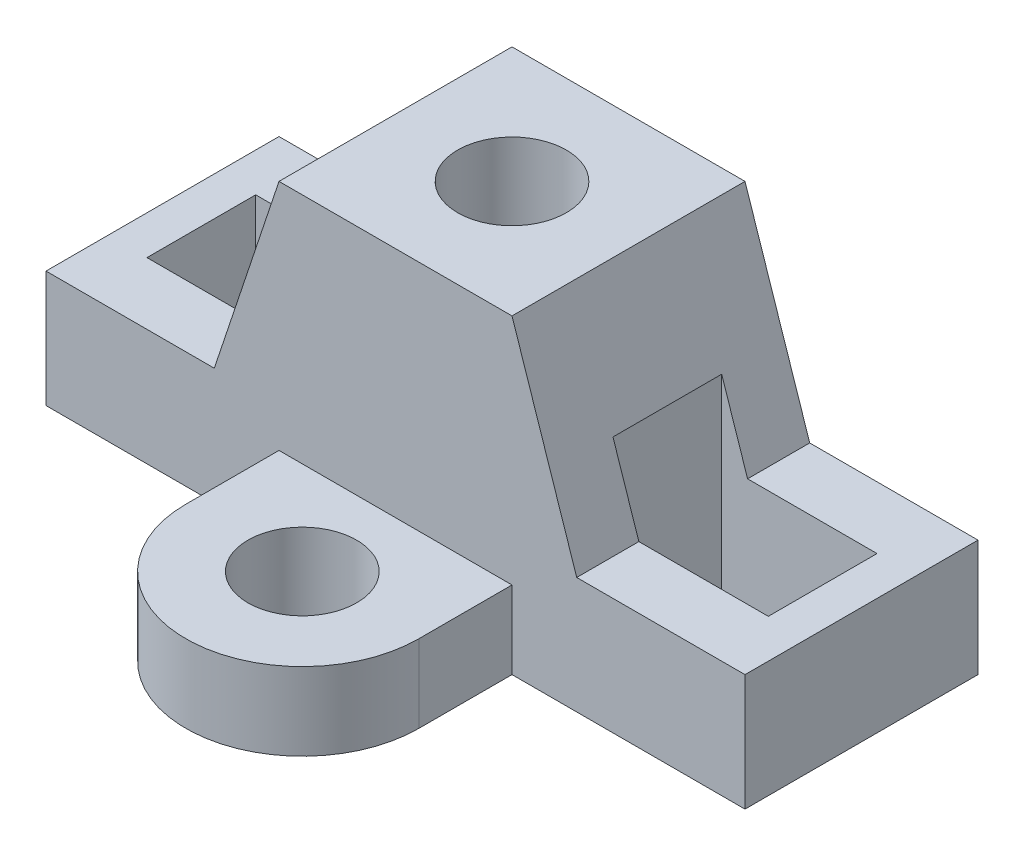
SolidWorks part; units mm, degrees
ref_plane "Front Plane" through (0, 0, 0) normal (0, 0, 1) x (1, 0, 0)
ref_plane "Top Plane" through (0, 0, 0) normal (0, 1, 0) x (1, 0, 0)
ref_plane "Right Plane" through (0, 0, 0) normal (1, 0, 0) x (0, 0, -1)
sketch "Sketch1" plane through (0, 0, 0) normal (0, 1, 0) x (1, 0, 0)
  line L0 (15, 0) -> (15, 12)
  line L1 (-15, 0) -> (-15, 12)
  line L2 (-15, 12) -> (15, 12)
  line L3 (-15, 12) -> (-15, 42)
  line L4 (-15, 42) -> (15, 42)
  line L5 (15, 42) -> (15, 12)
  line L6 (-15, 12) -> (15, 12)
  line L7 (15, 12) -> (45, 12)
  line L8 (-15, 12) -> (-45, 12)
  line L9 (-45, 12) -> (-45, 42)
  line L10 (-45, 42) -> (-15, 42)
  line L11 (15, 42) -> (45, 42)
  line L12 (45, 42) -> (45, 12)
  line L13 (-25, 42) -> (-25, 34)
  line L14 (25, 42) -> (25, 34)
  line L15 (-25, 12) -> (-25, 20)
  line L16 (-25, 34) -> (-25, 20)
  line L17 (-40, 34) -> (-40, 20)
  line L18 (-40, 34) -> (-25, 34)
  line L19 (-40, 20) -> (-25, 20)
  line L20 (25, 34) -> (45, 34)
  line L21 (45, 34) -> (45, 20)
  line L22 (45, 20) -> (25, 20)
  line L23 (25, 20) -> (25, 34)
  line L25 (25, 20) -> (25, 12)
  line L26 (40, 34) -> (40, 20)
  circle A0 centre (0, 0) radius 7
  arc A1 (-15, 0) -> (15, 0) centre (0, 0) ccw
  circle A2 centre (0, 27) radius 7
  dimension "D1" = 14
  dimension "D2" = 30
  dimension "D6" = 14
  dimension "D8" = 30
  dimension "D3" = 12
  dimension "D4" = 12
  dimension "D5" = 30
  dimension "D7" = 8
  dimension "D9" = 30
  dimension "D10" = 8
  dimension "D11" = 8
  dimension "D12" = 10
  dimension "D13" = 10
  dimension "D14" = 8
  dimension "D15" = 5
  dimension "D16" = 5
extrude "Boss-Extrude1" add sketch "Sketch1" along normal blind 10 contours L1 A1 L0 L2 A0 region at (0, 0, 14.5964)
extrude "Boss-Extrude2" add sketch "Sketch1<5>" along normal blind 40 contours L5 L4 L3 L2 A2 region at (0, 0, -12.4243)
sketch "Sketch1<5>" plane through (0, 0, 0) normal (0, 1, 0) x (1, 0, 0) same geometry as "Sketch1"
extrude "Boss-Extrude5" add sketch "Sketch1<11>" along normal blind 15 separate body contours L14 L20 L12 L11 | L20 L26 L22 L12 | L22 L25 L7 L12 region at (35, 0, -16) region at (35, 0, -38) region at (42.5, 0, -27)
sketch "Sketch1<11>" plane through (0, 0, 0) normal (0, 1, 0) x (1, 0, 0) same geometry as "Sketch1"
extrude "Boss-Extrude6" add sketch "Sketch1<12>" along normal blind 15 separate body contours L19 L17 L18 L13 L10 L9 L8 L15 region at (-35, 0, -12.3606)
sketch "Sketch1<12>" plane through (0, 0, 0) normal (0, 1, 0) x (1, 0, 0) same geometry as "Sketch1"
extrude "Boss-Extrude7" add sketch "Sketch1<13>" along normal blind 40 contours L13 L16 L15 L8 L3 L10 | L25 L23 L14 L11 L5 L7 region at (20, 0, -27) region at (-20, 0, -27)
sketch "Sketch1<13>" plane through (0, 0, 0) normal (0, 1, 0) x (1, 0, 0) same geometry as "Sketch1"
chamfer "Chamfer2" distance 30 distance2 10 2 edges at (25, 40, -27) (-25, 40, -27) first distance on face at (25, 17.5, -27) first distance on face at (-25, 17.5, -27)
sketch "Sketch4" plane through (0, 0, 0) normal (0, -1, 0) x (1, 0, 0)
  line L0 (-25, -20) -> (-20, -20)
  line L1 (-25, -34) -> (-20, -34)
  line L2 (-20, -20) -> (-20, -34)
  line L3 (-25, -20) -> (-25, -34)
  line L4 (0, 5.4032) -> (0, -45.9259) construction
  line L5 (25, -20) -> (20, -20)
  line L6 (20, -20) -> (20, -34)
  line L7 (25, -34) -> (20, -34)
  line L8 (25, -20) -> (25, -34)
  dimension "D1" = 20
extrude "Cut-Extrude3" cut sketch "Sketch4" against normal through all
